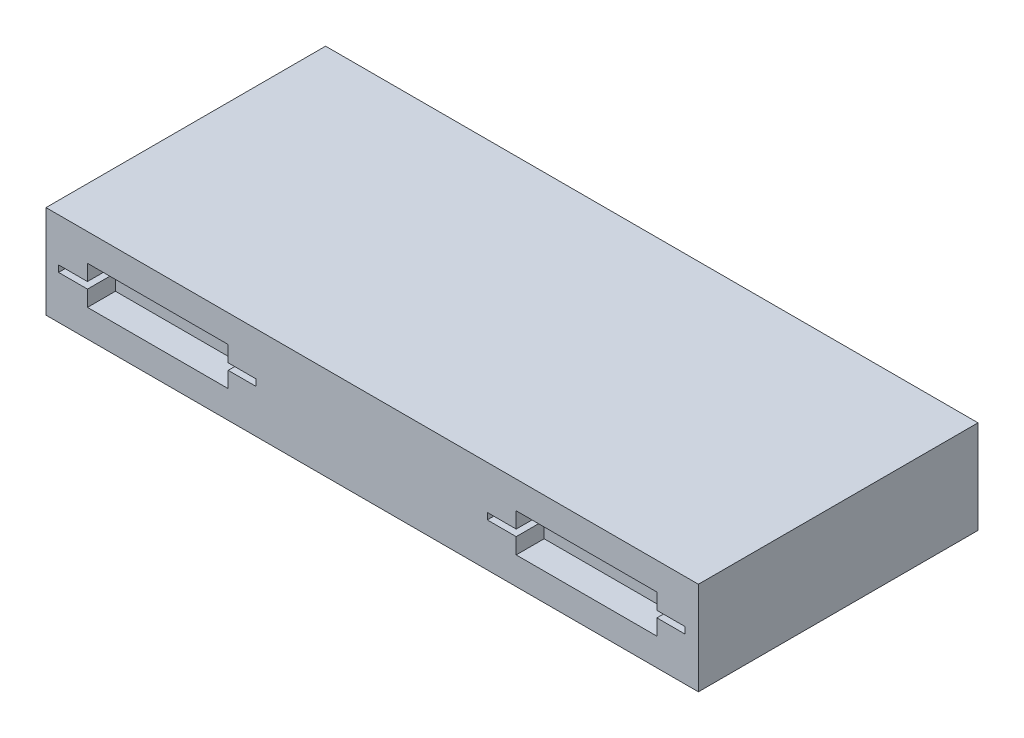
SolidWorks part; units mm, degrees
ref_plane "Front Plane" through (0, 0, 0) normal (0, 0, 1) x (1, 0, 0)
ref_plane "Top Plane" through (0, 0, 0) normal (0, 1, 0) x (1, 0, 0)
ref_plane "Right Plane" through (0, 0, 0) normal (1, 0, 0) x (0, 0, -1)
sketch "Sketch2" plane through (0, 0, 0) normal (0, 1, 0) x (1, 0, 0)
  line L1 (-250, -150) -> (450, -150)
  line L2 (-250, -150) -> (-250, 150)
  line L3 (-250, 150) -> (450, 150)
  line L4 (450, -150) -> (450, 150)
  point P0 (0, 0)
  dimension "D1" = 700
  dimension "D2" = 300
extrude "Boss-Extrude1" add sketch "Sketch2" along normal blind 100
sketch "Sketch4" plane through (0, 0, -150) normal (0, 0, -1) x (-1, 0, 0)
  line L5 (-435.5, 53.5) -> (-405.5, 53.5)
  line L6 (-405.5, 53.5) -> (-405.5, 70.5)
  line L17 (-405.5, 70.5) -> (-254.5, 70.5)
  line L18 (-254.5, 70.5) -> (-254.5, 53.5)
  line L19 (-254.5, 53.5) -> (-223.5, 53.5)
  line L20 (-223.5, 53.5) -> (-223.5, 46.5)
  line L21 (-223.5, 46.5) -> (-254.5, 46.5)
  line L22 (-254.5, 46.5) -> (-254.5, 29.5)
  line L23 (-254.5, 29.5) -> (-405.5, 29.5)
  line L24 (-405.5, 29.5) -> (-405.5, 46.5)
  line L25 (-405.5, 46.5) -> (-435.5, 46.5)
  line L26 (-435.5, 46.5) -> (-435.5, 53.5)
  line L27 (-405.5, 70.5) -> (-254.5, 29.5) construction
  line L28 (-254.5, 70.5) -> (-405.5, 29.5) construction
  line L29 (-450, 0) -> (250, 0) construction
  line L30 (-450, 100) -> (-450, 0) construction
  point P0 (-201.6164, 68.4615)
  point P3 (-330, 50)
  dimension "D1" = 151
  dimension "D2" = 17
  dimension "D3" = 17
  dimension "D4" = 31
  dimension "D5" = 30
  dimension "D6" = 7
  dimension "D7" = 50
  dimension "D8" = 120
extrude "Cut-Extrude2" cut sketch "Sketch4" against normal blind 30
sketch "Sketch5" plane through (0, 0, -150) normal (0, 0, -1) x (-1, 0, 0)
  line L5 (24.5, 53.5) -> (54.5, 53.5)
  line L6 (54.5, 53.5) -> (54.5, 70.5)
  line L7 (-450, 0) -> (250, 0) construction
  line L17 (54.5, 70.5) -> (205.5, 70.5)
  line L18 (205.5, 70.5) -> (205.5, 53.5)
  line L19 (205.5, 53.5) -> (236.5, 53.5)
  line L20 (236.5, 53.5) -> (236.5, 46.5)
  line L21 (236.5, 46.5) -> (205.5, 46.5)
  line L22 (205.5, 46.5) -> (205.5, 29.5)
  line L23 (205.5, 29.5) -> (54.5, 29.5)
  line L24 (54.5, 29.5) -> (54.5, 46.5)
  line L25 (54.5, 46.5) -> (24.5, 46.5)
  line L26 (24.5, 46.5) -> (24.5, 53.5)
  line L27 (54.5, 70.5) -> (205.5, 29.5) construction
  line L28 (205.5, 70.5) -> (54.5, 29.5) construction
  line L31 (250, 100) -> (250, 0) construction
  point P0 (228.0684, 74.1684)
  point P18 (130, 50)
  dimension "D1" = 151
  dimension "D2" = 17
  dimension "D3" = 17
  dimension "D4" = 31
  dimension "D5" = 30
  dimension "D6" = 7
  dimension "D7" = 120
  dimension "D8" = 50
extrude "Cut-Extrude3" cut sketch "Sketch5" against normal blind 30
ref_plane "Plane1" through (0, 0, 0) normal (0, 0, 1) x (1, 0, 0)
mirror "Mirror1" about plane through (0, 0, 0) normal (0, 0, 1) of "Cut-Extrude3", "Cut-Extrude2"
